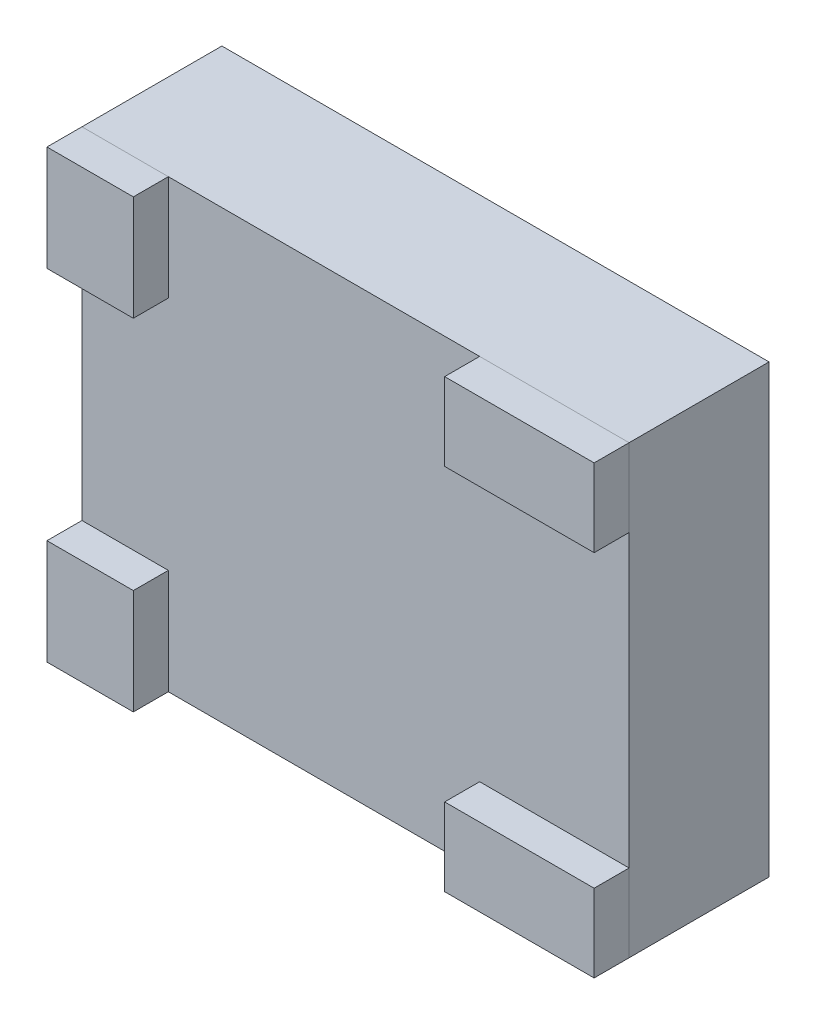
SolidWorks part; units mm, degrees
material "AISI 1020"
ref_plane "Plano superior" through (0, 0, 0) normal (0, 0, 1) x (1, 0, 0)
ref_plane "Plano frontal" through (0, 0, 0) normal (0, 1, 0) x (1, 0, 0)
ref_plane "Plano direito" through (0, 0, 0) normal (1, 0, 0) x (0, 0, -1)
other "Caixa delimitadora"
ref_plane "Default Plane" through (-78.1989, -63.755, 0) normal (0, 1, 0) x (1, 0, 0)
sketch "Esboço1" plane through (0, 0, 0) normal (0, 0, 1) x (1, 0, 0)
  line L1 (-78.1989, -63.755) -> (78.1989, -63.755)
  line L2 (-78.1989, -63.755) -> (-78.1989, 63.755)
  line L3 (-78.1989, 63.755) -> (78.1989, 63.755)
  line L4 (78.1989, -63.755) -> (78.1989, 63.755)
  line L5 (-78.1989, -63.755) -> (78.1989, 63.755) construction
  line L6 (-78.1989, 63.755) -> (78.1989, -63.755) construction
  circle A0 centre (0, 0) radius 15.125 construction
  point P0 (0, 0)
  dimension "D3" = 30.25
  dimension "D1" = 156.3979
  dimension "D2" = 127.51
extrude "A" add sketch "Esboço1" along normal blind 40
sketch "Esboço2" plane through (0, 0, 40) normal (0, 0, 1) x (1, 0, 0)
  line L0 (0, 0) -> (-78.1989, 0) construction
  line L1 (-78.1989, -63.755) -> (-53.5079, -63.755)
  line L2 (-78.1989, -63.755) -> (-78.1989, -33.6999)
  line L3 (-78.1989, -33.6999) -> (-53.5079, -33.6999)
  line L4 (-53.5079, -63.755) -> (-53.5079, -33.6999)
  line L5 (-78.1989, 63.755) -> (-78.1989, -63.755) construction
  line L6 (-78.1989, 33.6999) -> (-53.5079, 33.6999)
  line L7 (-53.5079, 63.755) -> (-53.5079, 33.6999)
  line L8 (-78.1989, 63.755) -> (-53.5079, 63.755)
  line L9 (-78.1989, 63.755) -> (-78.1989, 33.6999)
  line L10 (78.1989, 41.5261) -> (35.4788, 41.5261)
  line L11 (78.1989, -63.755) -> (35.4788, -63.755)
  line L12 (78.1989, -63.755) -> (78.1989, -41.5261)
  line L13 (78.1989, -41.5261) -> (35.4788, -41.5261)
  line L14 (35.4788, -63.755) -> (35.4788, -41.5261)
  line L15 (35.4788, 63.755) -> (35.4788, 41.5261)
  line L16 (78.1989, 63.755) -> (35.4788, 63.755)
  line L17 (78.1989, 63.755) -> (78.1989, 41.5261)
extrude "Ressalto-extrusão2" add sketch "Esboço2" along normal blind 10 separate body
